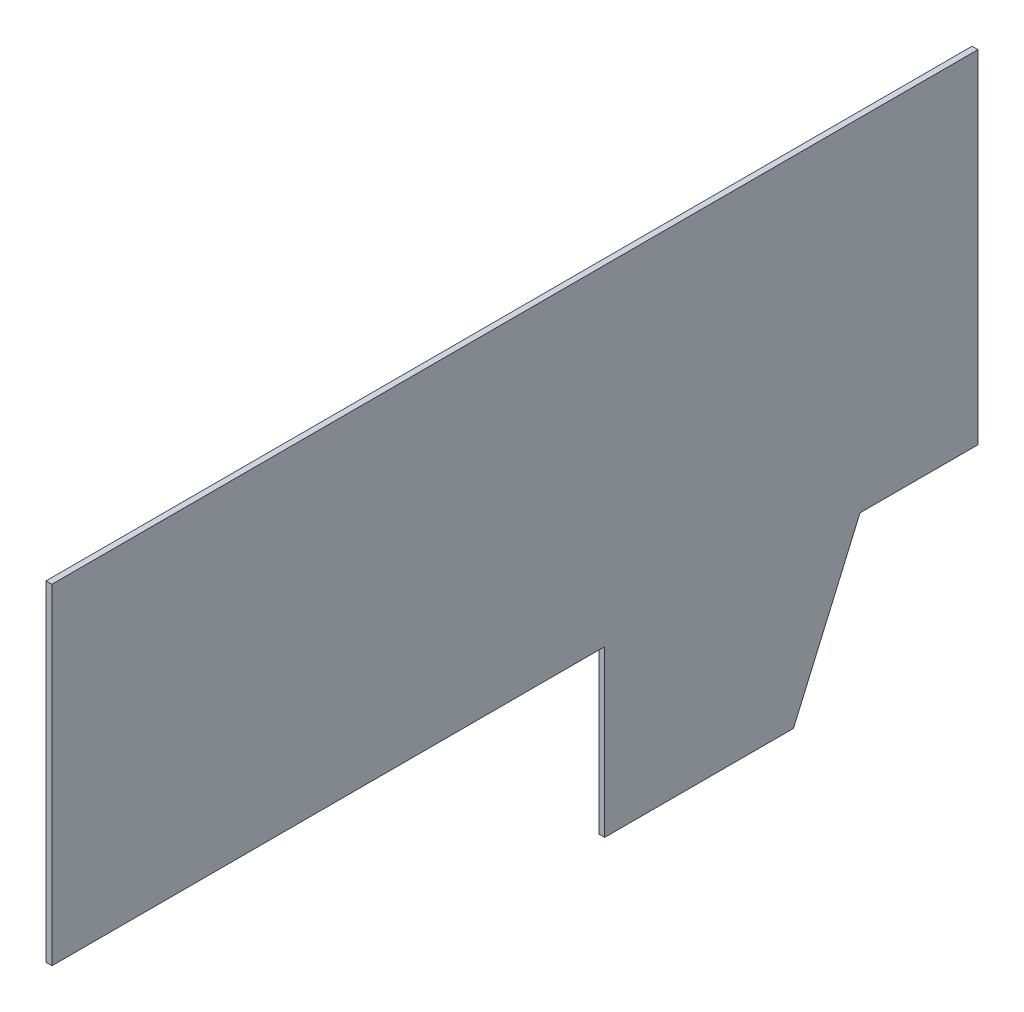
SolidWorks part; units mm, degrees
material "6061-T6 (SS)"
ref_plane "X-Y Datum" through (0, 0, 0) normal (0, 0, 1) x (1, 0, 0)
ref_plane "X-Z Datum" through (0, 0, 0) normal (0, 1, 0) x (1, 0, 0)
ref_plane "Y-Z Datum" through (0, 0, 0) normal (1, 0, 0) x (0, 0, -1)
sketch "Sketch1" plane through (0, 0, 0) normal (1, 0, 0) x (0, 0, -1)
  line L1 (-249.174, 88.9) -> (249.174, 88.9)
  line L2 (-249.174, 88.9) -> (-249.174, -88.9)
  line L3 (-249.174, -88.9) -> (249.174, -88.9)
  line L4 (249.174, 88.9) -> (249.174, -88.9)
  line L5 (-249.174, 88.9) -> (249.174, -88.9) construction
  line L6 (-249.174, -88.9) -> (249.174, 88.9) construction
  point P0 (0, 0)
  dimension "D1" = 177.8
  dimension "D2" = 498.348
extrude "Boss-Extrude1" add sketch "Sketch1" along normal mid plane 3.175
sketch "Sketch2" plane through (1.5875, 0, 0) normal (1, 0, 0) x (0, 0, -1)
  line L0 (249.174, -88.9) -> (249.174, -95.25)
  line L1 (249.174, -95.25) -> (185.674, -95.25)
  line L2 (185.674, -95.25) -> (149.8854, -177.8)
  line L3 (149.8854, -177.8) -> (48.2854, -177.8)
  line L4 (48.2854, -177.8) -> (48.2854, -88.9)
  line L5 (-249.174, -88.9) -> (249.174, -88.9) construction
  line L6 (48.2854, -88.9) -> (249.174, -88.9)
  line L8 (48.2854, -76.2) -> (48.2854, 88.9)
  line L10 (249.174, -88.9) -> (249.174, 88.9) construction
  line M10 (-249.174, -88.9) -> (249.174, -88.9)
  dimension "D1" = 6.35
  dimension "D2" = 63.5
  dimension "D3" = 88.9
  dimension "D4" = 101.6
extrude "Boss-Extrude2" add sketch "Sketch2" against normal blind 3.175 contours L4 L3 L2 L1 L0 M10 region at (1.5875, -129.6106, -113.0883)
